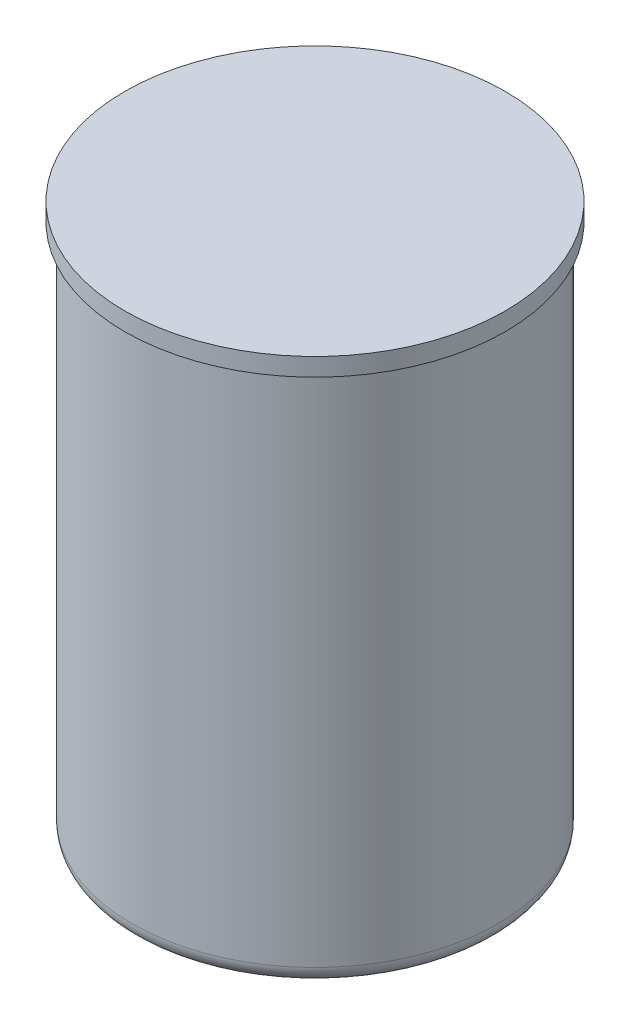
SolidWorks part; units mm, degrees
ref_plane "Alzado" through (0, 0, 0) normal (0, 0, 1) x (1, 0, 0)
ref_plane "Planta" through (0, 0, 0) normal (0, 1, 0) x (1, 0, 0)
ref_plane "Vista lateral" through (0, 0, 0) normal (1, 0, 0) x (0, 0, -1)
sketch "Croquis1" plane through (0, 0, 0) normal (0, 1, 0) x (1, 0, 0)
  circle A0 centre (0, 0) radius 50.8901
extrude "Saliente-Extruir1" add sketch "Croquis1" along normal blind 150
sketch "Croquis2" plane through (0, 150, 0) normal (0, 1, 0) x (1, 0, 0)
  circle A0 centre (0, 0) radius 17.5714
extrude "Cortar-Extruir1" cut sketch "Croquis2" against normal through all
sketch "Croquis3" plane through (0, 150, 0) normal (0, 1, 0) x (1, 0, 0)
  circle A0 centre (0, 0) radius 19.1218
  circle A1 centre (0, 0) radius 49.7184
extrude "Cortar-Extruir2" cut sketch "Croquis3" against normal blind 2.5
sketch "Croquis4" plane through (0, 0, 0) normal (0, -1, 0) x (1, 0, 0)
  circle A0 centre (0, 0) radius 17.8298
  circle A1 centre (0, 0) radius 19.4769
extrude "Saliente-Extruir3" add sketch "Croquis4" along normal blind 15
sketch "Croquis6" plane through (0, 0, 0) normal (0, -1, 0) x (1, 0, 0)
  circle A0 centre (0, 0) radius 21.5317
  circle A1 centre (0, 0) radius 49.2332
extrude "Cortar-Extruir4" cut sketch "Croquis6" against normal blind 5
sketch "Croquis8" plane through (0, 147.5, 0) normal (0, 1, 0) x (1, 0, 0)
  line L1 (0, 17.5714) -> (2.814, 17.5714)
  line L2 (0, 17.5714) -> (0, 11.9953)
  line L3 (0, 11.9953) -> (2.814, 11.9953)
  line L4 (2.814, 17.5714) -> (2.814, 11.9953)
  line L5 (0, -17.5714) -> (2.814, -17.5714)
  line L6 (0, -17.5714) -> (0, -11.9953)
  line L7 (0, -11.9953) -> (2.814, -11.9953)
  line L8 (2.814, -17.5714) -> (2.814, -11.9953)
  circle A0 centre (0, 0) radius 17.5714 construction
extrude "Saliente-Extruir6" add sketch "Croquis8" against normal blind 145
sketch "Croquis9" plane through (0, 147.5, 0) normal (0, 1, 0) x (1, 0, 0)
  circle A0 centre (0, 0) radius 19.463
  circle A1 centre (0, 0) radius 21.4211
extrude "Saliente-Extruir7" add sketch "Croquis9" along normal blind 2.5
fillet "Redondeo1" radius 5 1 edges at (0, 0, 50.8901)
fillet "Redondeo2" radius 5 1 edges at (0, -15, -19.4769)
fillet "Redondeo3" radius 5 1 edges at (0, 0, -21.5317)
fillet "Redondeo4" radius 5 1 edges at (0, 150, 50.8901)
fillet "Redondeo6" radius 2 1 edges at (0, 150, 21.4211)
sketch "Croquis10" plane through (0, 147.5, 0) normal (0, 1, 0) x (1, 0, 0)
  circle A0 centre (0, 0) radius 50.8901
extrude "Saliente-Extruir8" add sketch "Croquis10" against normal mid plane 10
sketch "Croquis11" plane through (0, 152.5, 0) normal (0, 1, 0) x (1, 0, 0)
  circle A0 centre (0, 0) radius 52.9568
extrude "Saliente-Extruir9" add sketch "Croquis11" against normal blind 5
sketch "Croquis12" plane through (0, 0, 0) normal (0, 0, 1) x (1, 0, 0)
  line L0 (0, -35.7614) -> (0, 184.0962) construction
  line L1 (2.9699, 147.5) -> (-2.9699, 147.5)
  line L2 (-50.8901, 147.5) -> (50.8901, 147.5) construction
  line L3 (-2.9699, 147.5) -> (-2.9699, 3.718)
  line L4 (-50.8901, 3.718) -> (50.8901, 3.718) construction
  line L5 (-2.9699, 3.718) -> (2.9699, 3.718)
  line L6 (2.9699, 3.718) -> (2.9699, 147.5)
extrude "Cortar-Extruir5" cut sketch "Croquis12" along normal blind 10
ref_axis "Eje1" through (0, 147.5, 0) along (0, -1, 0)
